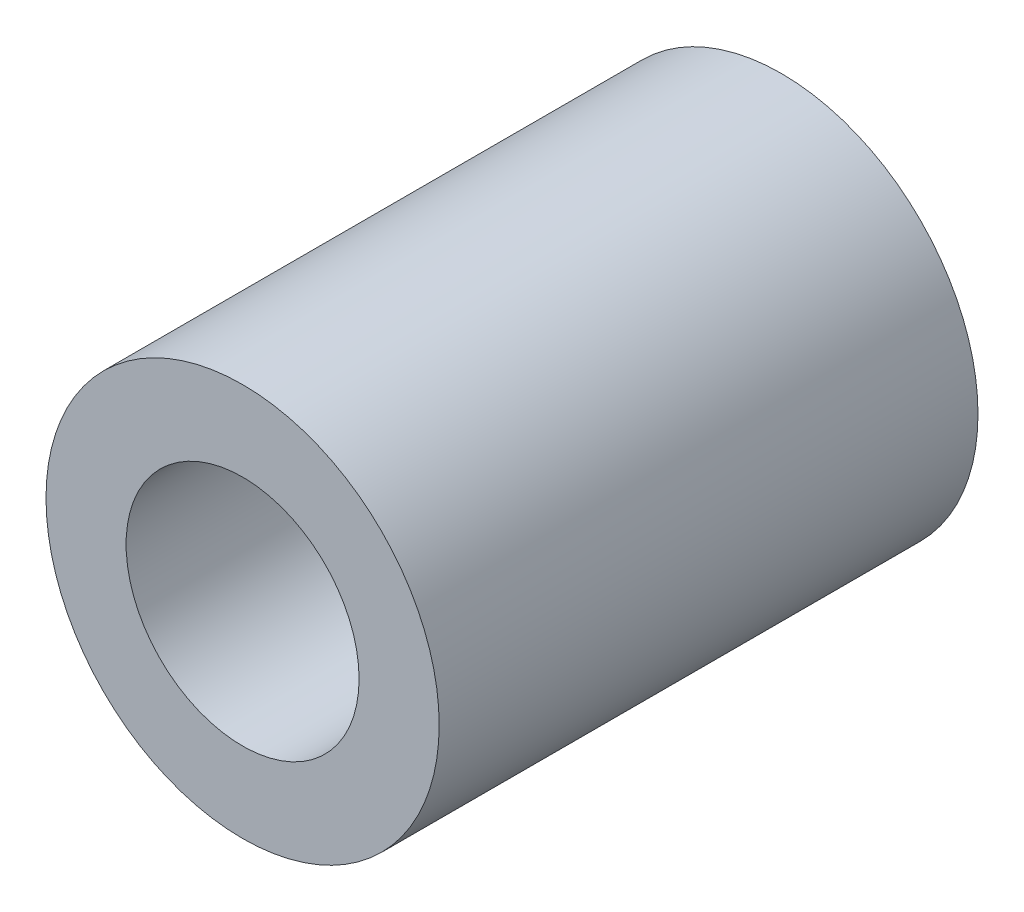
SolidWorks part; units mm, degrees
ref_plane "Front Plane" through (0, 0, 0) normal (0, 0, 1) x (1, 0, 0)
ref_plane "Top Plane" through (0, 0, 0) normal (0, 1, 0) x (1, 0, 0)
ref_plane "Right Plane" through (0, 0, 0) normal (1, 0, 0) x (0, 0, -1)
sketch "Sketch1" plane through (0, 0, 0) normal (0, 0, 1) x (1, 0, 0)
  circle A0 centre (0, 0) radius 8
  circle A1 centre (0, 0) radius 13.5
  dimension "D1" = 16
  dimension "D2" = 27
extrude "Boss-Extrude1" add sketch "Sketch1" along normal blind 18.5 and the other way blind 18.5
